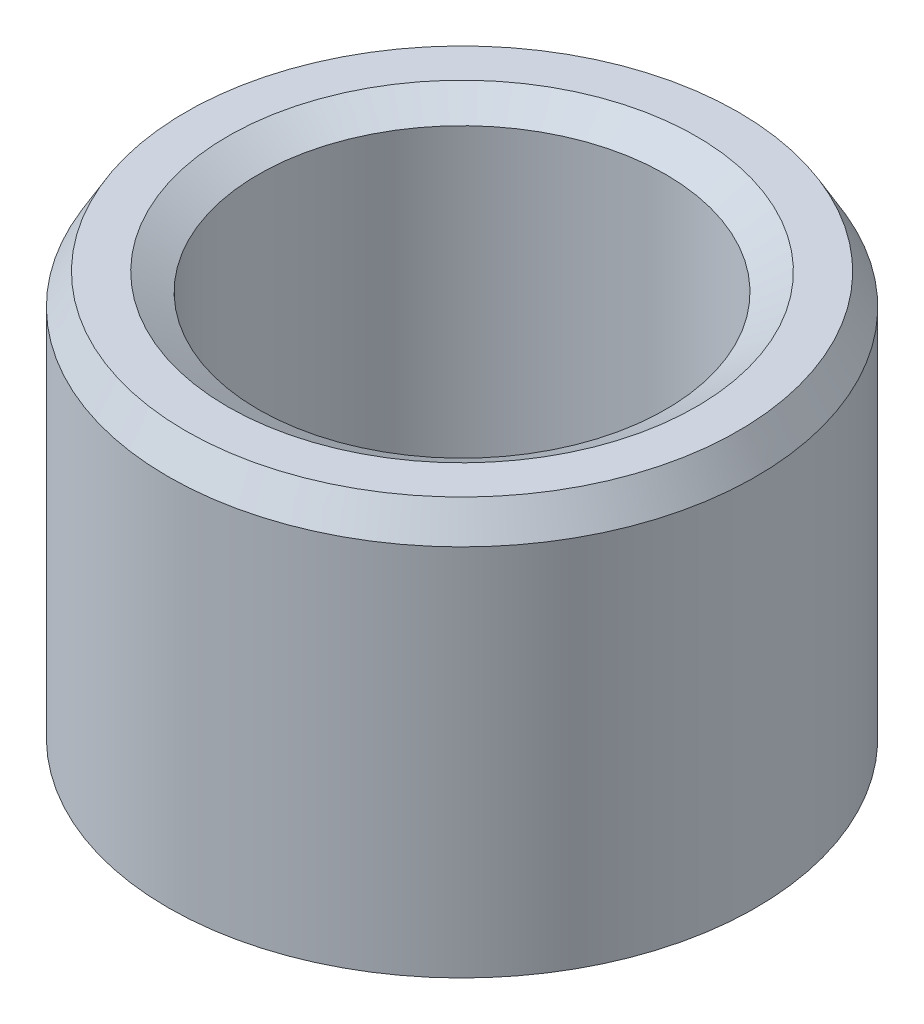
SolidWorks part; units mm, degrees
ref_plane "Front Plane" through (0, 0, 0) normal (0, 0, 1) x (1, 0, 0)
ref_plane "Top Plane" through (0, 0, 0) normal (0, 1, 0) x (1, 0, 0)
ref_plane "Right Plane" through (0, 0, 0) normal (1, 0, 0) x (0, 0, -1)
sketch "Sketch1" plane through (0, 0, 0) normal (0, 1, 0) x (1, 0, 0)
  circle A0 centre (0, 0) radius 35
  dimension "SLEEVE_OD" = 70
extrude "Boss-Extrude1" add sketch "Sketch1" along normal blind 50.2143
sketch "Sketch2" plane through (0, 0, 0) normal (0, 1, 0) x (1, 0, 0)
  circle A0 centre (0, 0) radius 24.2471
  dimension "BORE_D" = 48.4942
extrude "Cut-Extrude1" cut sketch "Sketch2" along normal through all
chamfer "Chamfer1" distance 3.6527 angle 30 4 edges at (0, 50.2143, 24.2471) (0, 0, 24.2471) (0, 0, 35) (0, 50.2143, 35) first distance on face at (0, 50.2143, 24.2471) first distance on face at (0, 0, 24.2471) first distance on face at (0, 50.2143, 35)
